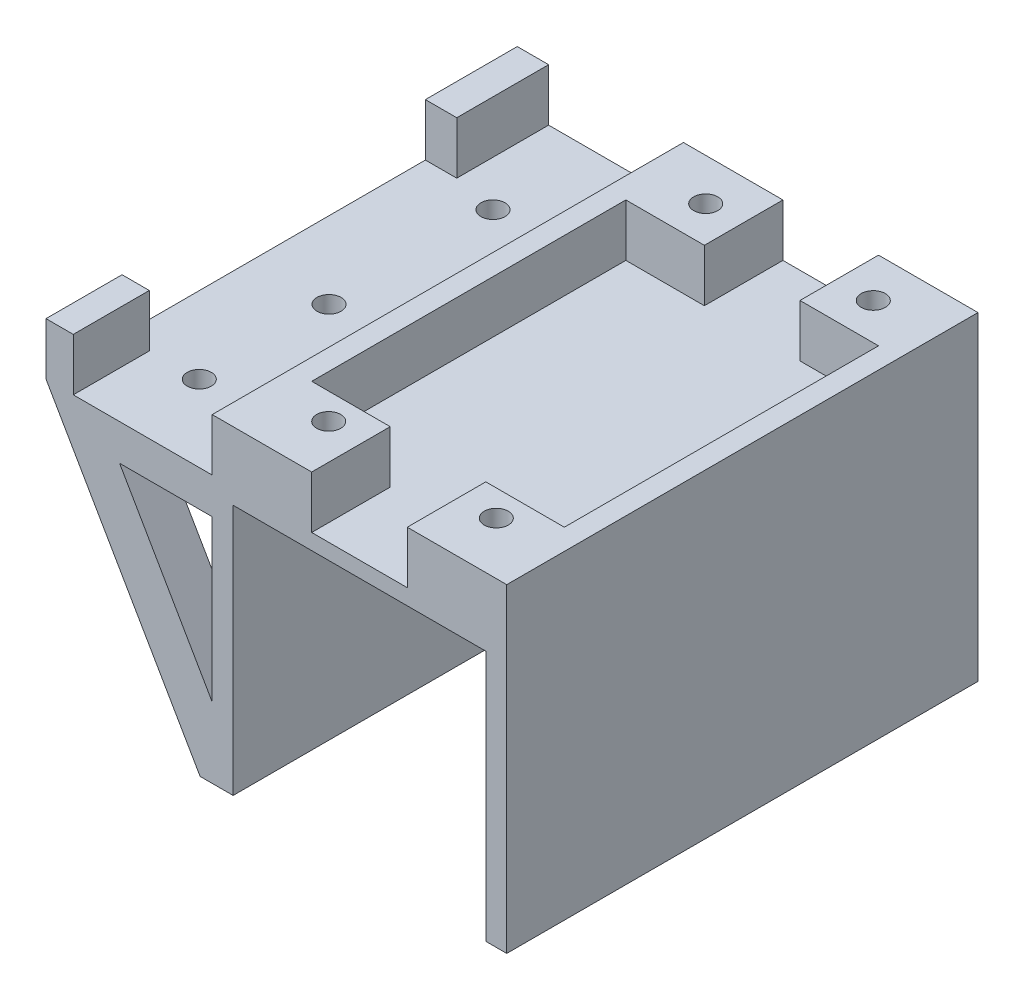
SolidWorks part; units mm, degrees
ref_plane "Front" through (0, 0, 0) normal (0, 0, 1) x (1, 0, 0)
ref_plane "Top" through (0, 0, 0) normal (0, 1, 0) x (1, 0, 0)
ref_plane "Right" through (0, 0, 0) normal (1, 0, 0) x (0, 0, -1)
sketch "Sketch1" plane through (0, 0, 0) normal (0, 0, 1) x (1, 0, 0)
  line L0 (0, 0) -> (0, 70)
  line L1 (0, 70) -> (56.254, 70)
  line L2 (56.254, 70) -> (56.254, 0)
  line L3 (56.254, 0) -> (52.254, 0)
  line L4 (52.254, 0) -> (52.254, 65)
  line L5 (52.254, 65) -> (4, 65)
  line L6 (4, 65) -> (4, 0)
  line L7 (4, 0) -> (0, 0)
  line L9 (4, 55) -> (52.254, 55)
  line L10 (4, 55) -> (4, 52)
  line L11 (4, 52) -> (52.254, 52)
  line L12 (52.254, 55) -> (52.254, 52)
  dimension "D1" = 48.254
  dimension "D2" = 4
  dimension "D3" = 4
  dimension "D4" = 5
  dimension "D5" = 70
  dimension "D6" = 3
  dimension "D7" = 10
extrude "Boss-Extrude1" add sketch "Sketch1" along normal blind 70 contours L7 L6 L5 L4 L3 L2 L1 L0 | L9 L12 L11 L10 region at (0.898, 35, 0)
sketch "Sketch3" plane through (0, 0, 70) normal (0, 0, 1) x (1, 0, 0)
  line L0 (0, 70) -> (-40.3946, 70)
  line L1 (-40.3946, 70) -> (0, 0.0344)
  line L2 (0, 0) -> (0, 70) construction
  line L3 (0, 0.0344) -> (0, 70)
  line L4 (0, 70) -> (0, 62.5)
  line L5 (0, 62.5) -> (-26, 62.5)
  line L6 (-26, 62.5) -> (0, 17.4667)
  line L7 (0, 17.4667) -> (0, 0.0344)
  line M11 (0, 70) -> (0, 0)
  dimension "D1" = 60
  dimension "D2" = 180
  dimension "D3" = 7.5
  dimension "D4" = 26
extrude "Boss-Extrude3" add sketch "Sketch3" against normal blind 8 contours L6 L5 L0 L1 M11 region at (-16.8587, 46.1047, 70)
sketch "Sketch4" plane through (0, 0, 0) normal (0, 0, -1) x (-1, 0, 0)
  line L0 (0, 70) -> (40.3946, 70)
  line L1 (40.3946, 70) -> (0, 0)
  line L2 (0, 0) -> (0, 17.4667)
  line L3 (0, 17.4667) -> (26, 62.5)
  line L4 (26, 62.5) -> (0, 62.5)
  line L5 (0, 62.5) -> (0, 70)
extrude "Boss-Extrude4" add sketch "Sketch4" against normal blind 8
ref_plane "Plane1" through (0, 0, 39) normal (0, 0, -1) x (-1, 0, 0)
sketch "Sketch5" plane through (0, 0, 39) normal (0, 0, -1) x (-1, 0, 0)
  line L0 (0, 62.5) -> (0, 70)
  line L1 (0, 70) -> (40.3946, 70)
  line L2 (40.3946, 70) -> (0, 0)
  line L3 (0, 0) -> (0, 17.4667)
  line L4 (0, 17.4667) -> (26, 62.5)
  line L5 (26, 62.5) -> (0, 62.5)
extrude "Boss-Extrude5" add sketch "Sketch5" along normal blind 8
sketch "Sketch6" plane through (0, 0, 0) normal (0, 0, -1) x (-1, 0, 0)
  line L5 (0, 62.5) -> (36.0666, 62.5)
  line L6 (0, 0) -> (40.3946, 70) construction
  line L7 (36.0666, 62.5) -> (40.3946, 70)
  line L8 (40.3946, 70) -> (0, 70)
  line L9 (40.3946, 70) -> (-56.254, 70) construction
  line L10 (0, 70) -> (0, 62.5)
  line L11 (-4, 0) -> (0, 0)
  line L12 (0, 0) -> (7.5019, 13)
  line L13 (7.5019, 13) -> (-4, 13)
  line L14 (-4, 52) -> (-4, 0) construction
  line L15 (-4, 13) -> (-4, 0)
  dimension "D1" = 13
extrude "Boss-Extrude6" add sketch "Sketch6" against normal blind 70
sketch "Sketch7" plane through (0, 0, 70) normal (0, 0, 1) x (1, 0, 0)
  line L0 (0, 17.4667) -> (0, 62.5) construction
  line L1 (-40.3946, 70) -> (0, 70)
  line L2 (-40.3946, 70) -> (-40.3946, 53)
  line L3 (-40.3946, 53) -> (0, 53)
  line L4 (0, 70) -> (0, 53)
  dimension "D1" = 17
extrude "Cut-Extrude3" cut sketch "Sketch7" against normal blind 70
sketch "Sketch8" plane through (0, 0, 0) normal (0, 0, -1) x (-1, 0, 0)
  line L1 (-4, 55) -> (-4, 52)
  line L2 (-4, 52) -> (-52.254, 52) construction
  line L3 (-4, 52) -> (30.0074, 52)
  line L4 (0, 0) -> (30.5845, 53) construction
  line L6 (30.0074, 52) -> (31.7386, 55)
  line L7 (31.7386, 55) -> (-4, 55)
  dimension "D1" = 180
extrude "Boss-Extrude7" add sketch "Sketch8" against normal blind 70
sketch "Sketch11" plane through (0, 0, 70) normal (0, 0, 1) x (1, 0, 0)
  line L0 (-31.7386, 55) -> (0, 0)
  line L3 (-31.7386, 55) -> (0, 55) construction
  line L4 (-27.289, 55) -> (-31.7386, 55)
  line L5 (-27.289, 55) -> (-3.0537, 13)
  line L6 (-3.0537, 13) -> (0, 0)
extrude "Boss-Extrude10" add sketch "Sketch11" against normal blind 8
sketch "Sketch12" plane through (0, 0, 70) normal (0, 0, 1) x (1, 0, 0)
  line L0 (-31.7386, 55) -> (-27.7598, 48.1051)
  line L1 (0, 0) -> (-31.7386, 55) construction
  line L2 (-27.7598, 48.1051) -> (0, 48.1051)
  line L3 (0, 17.4667) -> (0, 52) construction
  line L4 (0, 48.1051) -> (0, 55)
  line L5 (0, 55) -> (-31.7386, 55)
extrude "Boss-Extrude11" add sketch "Sketch12" against normal blind 70
sketch "Sketch13" plane through (0, 0, 0) normal (0, -1, 0) x (1, 0, 0)
  line L1 (67.4394, -10.6205) -> (-15.562, -10.6205)
  line L2 (67.4394, -10.6205) -> (67.4394, 77.2481)
  line L3 (67.4394, 77.2481) -> (-15.562, 77.2481)
  line L4 (-15.562, -10.6205) -> (-15.562, 77.2481)
extrude "Cut-Extrude4" cut sketch "Sketch13" against normal blind 4
sketch "Sketch14" plane through (0, 0, 70) normal (0, 0, 1) x (1, 0, 0)
  line L0 (-2.3083, 4) -> (-31.7386, 55)
  line L1 (-31.7386, 55) -> (0, 55)
  line L2 (0, 55) -> (0, 70)
  line L3 (0, 70) -> (56.254, 70)
  line L4 (56.254, 70) -> (56.254, 4)
  line L5 (56.254, 4) -> (52.254, 4)
  line L6 (52.254, 4) -> (52.254, 52)
  line L7 (52.254, 52) -> (4, 52)
  line L8 (4, 52) -> (4, 4)
  line L9 (4, 4) -> (-2.3083, 4)
  line L14 (-17.6891, 48.1051) -> (0, 48.1051)
  line L15 (52.254, 55) -> (4, 55)
  line L16 (52.254, 55) -> (52.254, 65)
  line L17 (52.254, 65) -> (4, 65)
  line L18 (4, 55) -> (4, 65)
  line L19 (-17.6891, 48.1051) -> (0, 48.1051) construction
  line L20 (0, 48.1051) -> (0, 17.4667)
  line L21 (0, 17.4667) -> (-17.6891, 48.1051)
extrude "Boss-Extrude12" add sketch "Sketch14" along normal blind 20
sketch "Sketch15" plane through (0, 0, 90) normal (0, 0, 1) x (1, 0, 0)
  line L0 (56.254, 4) -> (56.254, 70) construction
  line L1 (56.254, 65) -> (37.264, 65)
  line L2 (56.254, 65) -> (56.254, 55)
  line L3 (56.254, 55) -> (37.264, 55)
  line L4 (37.264, 65) -> (37.264, 55)
  line L5 (4, 55) -> (52.254, 55) construction
  dimension "D1" = 18.99
sketch "Sketch16" plane through (0, 0, 90) normal (0, 0, 1) x (1, 0, 0)
  line L1 (0, 70) -> (56.254, 70)
  line L2 (0, 70) -> (0, 65)
  line L3 (0, 65) -> (56.254, 65)
  line L4 (56.254, 70) -> (56.254, 65)
extrude "Cut-Extrude5" cut sketch "Sketch16" against normal blind 100
sketch "Sketch17" plane through (0, 65, 0) normal (0, 1, 0) x (1, 0, 0)
  line L1 (52.254, 0) -> (37.254, 0)
  line L2 (52.254, 0) -> (52.254, -15)
  line L3 (52.254, -15) -> (37.254, -15)
  line L4 (37.254, 0) -> (37.254, -15)
  line L5 (52.254, -90) -> (37.254, -90)
  line L6 (52.254, -90) -> (52.254, -75)
  line L7 (52.254, -75) -> (37.254, -75)
  line L8 (37.254, -90) -> (37.254, -75)
  dimension "D1" = 15
  dimension "D2" = 15
  dimension "D3" = 15
  dimension "D4" = 15
extrude "Boss-Extrude14" add sketch "Sketch17" against normal blind 13
sketch "Sketch21" plane through (0, 52, 0) normal (0, -1, 0) x (-1, 0, 0)
  circle A0 centre (-44.254, -80) radius 2.3
  circle A1 centre (-44.254, -8) radius 2.3
sketch "Sketch22" plane through (0, 52, 0) normal (0, -1, 0) x (1, 0, 0)
  line L1 (48.0965, 6.0036) -> (47.9041, 10.3295)
  line L2 (47.9041, 10.3295) -> (44.0617, 12.3259)
  line L3 (44.0617, 12.3259) -> (40.4115, 9.9964)
  line L4 (40.4115, 9.9964) -> (40.6039, 5.6705)
  line L5 (40.6039, 5.6705) -> (44.4463, 3.6741)
  line L6 (44.4463, 3.6741) -> (48.0965, 6.0036)
  line L7 (45.2007, 75.7746) -> (48.3866, 78.7072)
  line L8 (48.3866, 78.7072) -> (47.4399, 82.9325)
  line L9 (47.4399, 82.9325) -> (43.3073, 84.2254)
  line L10 (43.3073, 84.2254) -> (40.1214, 81.2928)
  line L11 (40.1214, 81.2928) -> (41.0681, 77.0675)
  line L12 (41.0681, 77.0675) -> (45.2007, 75.7746)
  circle A0 centre (44.254, 8) radius 3.75 construction
  circle A1 centre (44.254, 80) radius 3.75 construction
  point P10 (42.2366, 11.1611)
  dimension "D1" = 7.5
  dimension "D2" = 7.5
extrude "Cut-Extrude8" cut sketch "Sketch22" against normal blind 5
extrude "Cut-Extrude9" cut sketch "Sketch21" against normal blind 15
sketch "Sketch23" plane through (0, 0, 0) normal (-0.8661, -0.4998, 0) x (0, 0, 1)
  line L0 (90, 63.5007) -> (90, 4.6182) construction
  line L1 (70, 55.5401) -> (82, 55.5401)
  line L2 (70, 55.5401) -> (70, 15.0093)
  line L3 (70, 15.0093) -> (82, 15.0093)
  line L4 (82, 55.5401) -> (82, 15.0093)
  line L5 (62, 55.5401) -> (62, 15.0093) construction
  dimension "D1" = 8
  dimension "D2" = 8
extrude "Cut-Extrude10" cut sketch "Sketch23" against normal blind 9
sketch "Sketch25" plane through (0, 48.1051, 0) normal (0, -1, 0) x (-1, 0, 0)
  circle A0 centre (17.0755, -19.3006) radius 2.3
  circle A1 centre (17.0755, -50.6137) radius 2.3
extrude "Cut-Extrude11" cut sketch "Sketch25" against normal blind 20
sketch "Sketch26" plane through (0, 48.1051, 0) normal (0, -1, 0) x (1, 0, 0)
  circle A0 centre (-17.0755, 75.3913) radius 2.3
extrude "Cut-Extrude12" cut sketch "Sketch26" against normal blind 20
sketch "Sketch27" plane through (0, 0, 90) normal (0, 0, 1) x (1, 0, 0)
  line L0 (-23.3104, 48.1051) -> (-27.7598, 48.1051)
  line L1 (-31.7386, 55) -> (-2.3083, 4) construction
  line L2 (-27.7598, 48.1051) -> (-31.7386, 55)
  line L3 (-31.7386, 55) -> (-23.3104, 55)
  line L4 (0, 55) -> (-31.7386, 55) construction
  line L5 (-23.3104, 55) -> (-23.3104, 48.1051)
extrude "Boss-Extrude16" add sketch "Sketch27" against normal blind 20
sketch "Sketch28" plane through (0, 55, 0) normal (0, 1, 0) x (1, 0, 0)
  line L0 (4, -90) -> (37.254, -90) construction
  line L1 (4, 0) -> (19, 0)
  line L2 (4, 0) -> (4, -15)
  line L3 (4, -15) -> (19, -15)
  line L4 (19, 0) -> (19, -15)
  line L5 (4, -90) -> (19, -90)
  line L6 (4, -90) -> (4, -75)
  line L7 (4, -75) -> (19, -75)
  line L8 (19, -90) -> (19, -75)
  line L9 (4, 0) -> (4, -90) construction
  dimension "D1" = 15
  dimension "D2" = 15
  dimension "D3" = 15
  dimension "D4" = 15
extrude "Boss-Extrude17" add sketch "Sketch28" along normal blind 10
sketch "Sketch29" plane through (0, 52, 0) normal (0, -1, 0) x (-1, 0, 0)
  circle A0 centre (-12.254, -8) radius 2.3
  circle A1 centre (-12.254, -80) radius 2.3
extrude "Cut-Extrude13" cut sketch "Sketch29" against normal blind 20
sketch "Sketch30" plane through (0, 48.1051, 0) normal (0, -1, 0) x (1, 0, 0)
  line L1 (-27.7598, 70) -> (-17.3688, 70)
  line L2 (-27.7598, 70) -> (-27.7598, 82)
  line L3 (-27.7598, 82) -> (-17.3688, 82)
  line L4 (-17.3688, 70) -> (-17.3688, 82)
extrude "Boss-Extrude18" add sketch "Sketch30" against normal blind 5
sketch "Sketch31" plane through (0, 48.1051, 0) normal (0, -1, 0) x (1, 0, 0)
  circle A0 centre (-17.0755, 75.3913) radius 2.3
extrude "Cut-Extrude14" cut sketch "Sketch31" against normal blind 45
sketch "Sketch33" plane through (0, 55, 0) normal (0, 1, 0) x (1, 0, 0)
  circle A0 centre (27.6164, -46.5233) radius 1
  circle A1 centre (26.8974, -20.9206) radius 1
  circle A2 centre (28.9102, -66.6327) radius 1
  circle A3 centre (-20.9687, -5.2719) radius 1
  circle A4 centre (-23.4497, -23.5026) radius 1
  circle A5 centre (-17.8546, -42.0102) radius 1
  circle A6 centre (-22.4497, -64.7625) radius 1
  circle A7 centre (-17.8546, -85.6157) radius 1
sketch "Sketch34" plane through (0, 55, 0) normal (0, 1, 0) x (1, 0, 0)
  line L1 (-31.7386, -90) -> (-26.5312, -90)
  line L2 (-31.7386, -90) -> (-31.7386, -75.4774)
  line L3 (-31.7386, -75.4774) -> (-26.5312, -75.4774)
  line L4 (-26.5312, -90) -> (-26.5312, -75.4774)
  line L5 (-31.7386, 0) -> (-25.7455, 0)
  line L6 (-31.7386, 0) -> (-31.7386, -17.5484)
  line L7 (-31.7386, -17.5484) -> (-25.7455, -17.5484)
  line L8 (-25.7455, 0) -> (-25.7455, -17.5484)
extrude "Boss-Extrude19" add sketch "Sketch34" along normal blind 10
